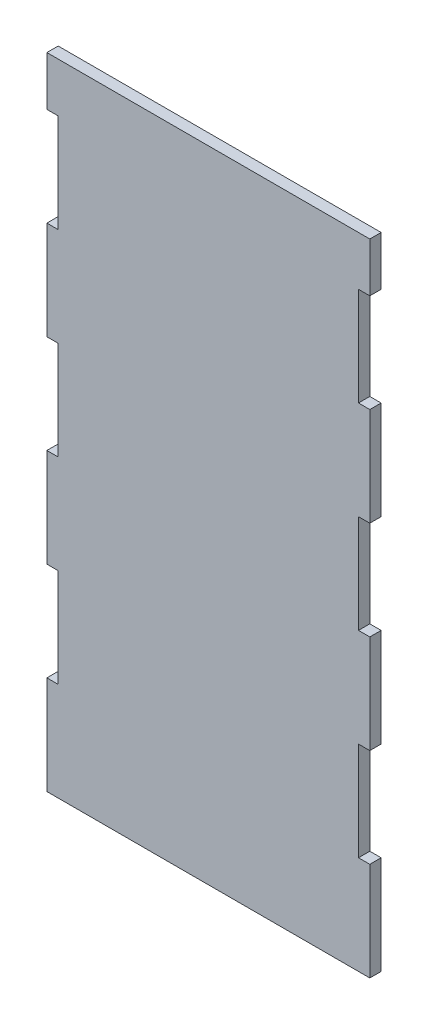
SolidWorks part; units mm, degrees
ref_plane "Front Plane" through (0, 0, 0) normal (0, 0, 1) x (1, 0, 0)
ref_plane "Top Plane" through (0, 0, 0) normal (0, 1, 0) x (1, 0, 0)
ref_plane "Right Plane" through (0, 0, 0) normal (1, 0, 0) x (0, 0, -1)
sketch "Sketch1" plane through (0, 0, 0) normal (0, 0, 1) x (1, 0, 0)
  line L1 (-41.656, 82.55) -> (41.656, 82.55)
  line L2 (-41.656, 82.55) -> (-41.656, -82.55)
  line L3 (-41.656, -82.55) -> (41.656, -82.55)
  line L4 (41.656, 82.55) -> (41.656, -82.55)
  point P4 (0, 82.55)
  point P6 (-41.656, 0)
  dimension "D1" = 83.312
  dimension "D2" = 165.1
extrude "Boss-Extrude1" add sketch "Sketch1" along normal mid plane 2.921
sketch "Sketch2" plane through (0, 0, 1.4605) normal (0, 0, 1) x (1, 0, 0)
  line L0 (-38.735, -82.55) -> (38.735, -82.55)
  line L1 (-41.656, 82.55) -> (41.656, 82.55)
  line L2 (-41.656, 82.55) -> (-41.656, -82.55)
  line L3 (-41.656, -82.55) -> (-38.735, -82.55)
  line L4 (41.656, 82.55) -> (41.656, -82.55)
  line L5 (38.735, -82.55) -> (41.656, -82.55)
  line L6 (-41.656, 82.55) -> (-38.735, 82.55)
  line L7 (-41.656, 82.55) -> (-41.656, -82.55)
  line L8 (-41.656, -82.55) -> (-38.735, -82.55)
  line L9 (-38.735, 82.55) -> (-38.735, -82.55)
  line L10 (41.656, 82.55) -> (38.735, 82.55)
  line L11 (41.656, 82.55) -> (41.656, -82.55)
  line L12 (41.656, -82.55) -> (38.735, -82.55)
  line L13 (38.735, 82.55) -> (38.735, -82.55)
  line L14 (-41.656, -57.15) -> (-38.735, -57.15)
  line L15 (38.735, -57.15) -> (41.656, -57.15)
  line L16 (-41.656, -31.75) -> (-38.735, -31.75)
  line L17 (38.735, -31.75) -> (41.656, -31.75)
  line L18 (-41.656, -6.35) -> (-38.735, -6.35)
  line L19 (38.735, -6.35) -> (41.656, -6.35)
  line L20 (-41.656, 19.05) -> (-38.735, 19.05)
  line L21 (38.735, 19.05) -> (41.656, 19.05)
  line L22 (-41.656, 44.45) -> (-38.735, 44.45)
  line L23 (38.735, 44.45) -> (41.656, 44.45)
  line L24 (-41.656, 69.85) -> (-38.735, 69.85)
  line L25 (38.735, 69.85) -> (41.656, 69.85)
  line L26 (-41.656, -82.55) -> (-41.656, -57.15) construction
  point P13 (0, 0)
  point P39 (0, 0)
  dimension "D1" = 2.921
  dimension "D2" = 2.921
  dimension "D4" = 25.4
  dimension "D5" = 2.921
  dimension "D6" = 2.921
  dimension "D3" = 7
extrude "Cut-Extrude1" cut sketch "Sketch2" against normal blind 2.921 contours L24 L7 L22 L9 | L20 L7 L18 L9 | L16 L7 L14 L9 | L17 L13 L15 L11 | L21 L13 L19 L11 | L25 L13 L23 L11 region at (-40.1955, -44.45, 1.4605) region at (40.1955, -44.45, 1.4605) region at (-40.1955, 6.35, 1.4605) region at (40.1955, 6.35, 1.4605) region at (-40.1955, 57.15, 1.4605) region at (40.1955, 57.15, 1.4605)
